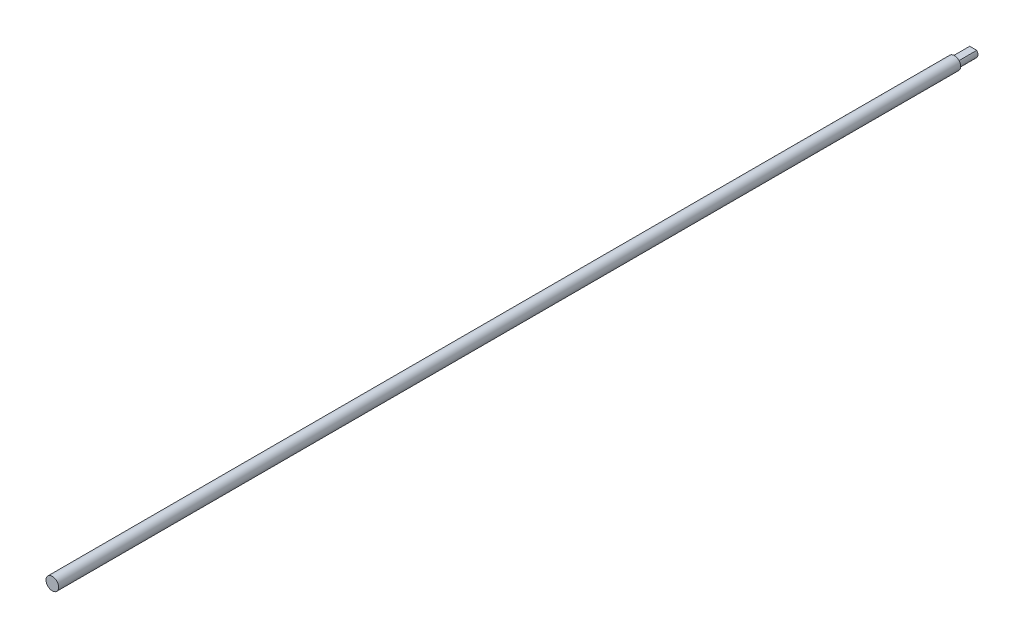
SolidWorks part; units mm, degrees
material "Barra Redonda SAE 1020 - 1/2\""
ref_plane "Plano frontal" through (0, 0, 0) normal (0, 0, 1) x (1, 0, 0)
ref_plane "Plano superior" through (0, 0, 0) normal (0, 1, 0) x (1, 0, 0)
ref_plane "Plano direito" through (0, 0, 0) normal (1, 0, 0) x (0, 0, -1)
sketch "Esboço1" plane through (0, 0, 0) normal (0, 0, 1) x (1, 0, 0)
  circle A0 centre (0, 0) radius 6.35
  dimension "D1" = 12.7
extrude "Ressalto-extrusão1" add sketch "Esboço1" along normal blind 584
sketch "Esboço2" plane through (0, 0, 584) normal (0, 0, 1) x (1, 0, 0)
  circle A0 centre (0, 0) radius 4
  circle A1 centre (0, 0) radius 12.7
  dimension "D1" = 8
extrude "Corte-extrusão1" cut sketch "Esboço2" against normal through all
sketch "Esboço3" plane through (0, 0, 0) normal (1, 0, 0) x (0, 0, -1)
  line L0 (0, -4) -> (0, 4) construction
  line L1 (0, 2) -> (-12, 2)
  line L2 (0, 2) -> (0, 12)
  line L3 (0, 12) -> (-12, 12)
  line L4 (-12, 2) -> (-12, 12)
  line L5 (0, 0) -> (-37.9294, 0) construction
  dimension "D1" = 12
  dimension "D2" = 10
  dimension "D3" = 2
extrude "Corte-extrusão2" cut sketch "Esboço3" against normal blind 10 and the other way blind 10
sketch "Esboço5" plane through (0, 0, 0) normal (0, 1, 0) x (1, 0, 0)
  line L0 (3.4641, 0) -> (-3.4641, 0) construction
  line L1 (-3, 0) -> (-13, 0)
  line L2 (-3, 0) -> (-3, -12)
  line L3 (-3, -12) -> (-13, -12)
  line L4 (-13, 0) -> (-13, -12)
  line L5 (3.4641, -12) -> (-3.4641, -12) construction
  line L6 (0, 0) -> (0, -29.1524) construction
  dimension "D1" = 6
  dimension "D2" = 10
revolve "Corte-Revolução2" cut sketch "Esboço5" angle 360 about L6
